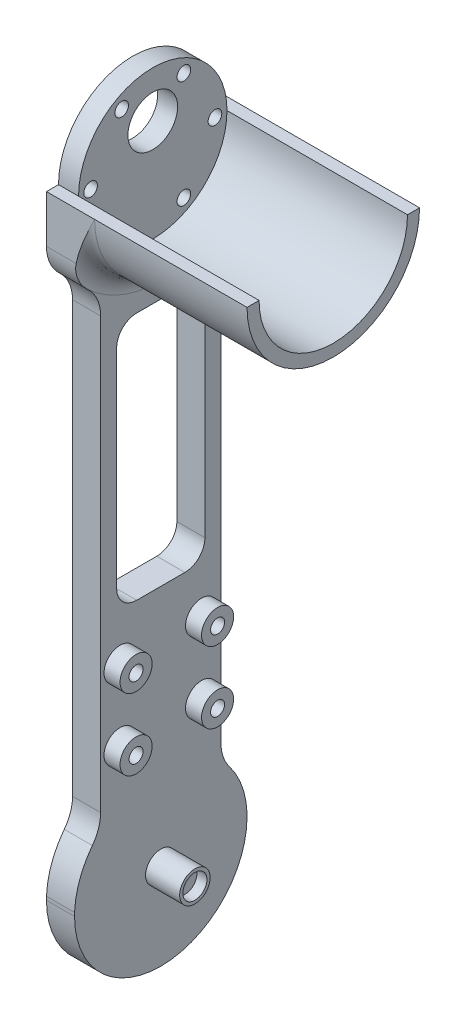
SolidWorks part; units mm, degrees
ref_plane "Front Plane" through (0, 0, 0) normal (0, 0, 1) x (1, 0, 0)
ref_plane "Top Plane" through (0, 0, 0) normal (0, 1, 0) x (1, 0, 0)
ref_plane "Right Plane" through (0, 0, 0) normal (1, 0, 0) x (0, 0, -1)
sketch "Sketch1" plane through (0, 0, 0) normal (1, 0, 0) x (0, 0, -1)
  circle A0 centre (0, 0) radius 18.5
  dimension "D1" = 37
extrude "Boss-Extrude1" add sketch "Sketch1" along normal blind 5
sketch "Sketch2" plane through (5, 0, 0) normal (1, 0, 0) x (0, 0, -1)
  circle A0 centre (0, 7) radius 6.2
  dimension "D1" = 12.4
  dimension "D2" = 7
extrude "Cut-Extrude1" cut sketch "Sketch2" against normal blind 10
sketch "Sketch3" plane through (0, 0, 0) normal (1, 0, 0) x (0, 0, -1)
  line L0 (0, 0) -> (0, 15.5) construction
  line L1 (0, 0) -> (7.75, 13.4234) construction
  line L2 (0, 0) -> (-15.5, 0) construction
  circle A0 centre (0, 0) radius 15.5 construction
  circle A1 centre (15.5, 0) radius 1.7
  circle A2 centre (7.75, -13.4234) radius 1.7
  circle A3 centre (-7.75, -13.4234) radius 1.7
  circle A4 centre (-15.5, 0) radius 1.7
  circle A5 centre (-7.75, 13.4234) radius 1.7
  circle A6 centre (7.75, 13.4234) radius 1.7
  point P17 (0, 0)
  dimension "D1" = 31
  dimension "D2" = 3.4
  dimension "D4" = 30
  dimension "D3" = 6
extrude "Cut-Extrude2" cut sketch "Sketch3" along normal blind 10
sketch "Sketch4" plane through (0, 0, 0) normal (-1, 0, 0) x (0, 0, 1)
  line L0 (-18.5, 0) -> (-21.5, 0)
  line L1 (18.5, 0) -> (21.5, 0)
  arc A0 (-21.5, 0) -> (21.5, 0) centre (0, 0) ccw
  circle A1 centre (0, 0) radius 18.5 construction
  arc A2 (-18.5, 0) -> (18.5, 0) centre (0, 0) ccw
  dimension "D1" = 3
extrude "Boss-Extrude2" add sketch "Sketch4" against normal blind 50
sketch "Sketch5" plane through (0, 0, 0) normal (-1, 0, 0) x (0, 0, 1)
  line L0 (-21.5, 0) -> (-18.5, 0)
  line L1 (18.5, 0) -> (21.5, 0)
  line L2 (-21.5, 0) -> (-21.5, -174.5)
  line L3 (21.5, 0) -> (21.5, -174.5)
  line L4 (21.5, -174.5) -> (-21.5, -174.5)
  arc A1 (-18.5, 0) -> (18.5, 0) centre (0, 0) ccw
  dimension "D1" = 174.5
extrude "Boss-Extrude3" add sketch "Sketch5" against normal blind 7
sketch "Sketch6" plane through (7, 0, 0) normal (1, 0, 0) x (0, 0, -1)
  line L0 (21.5, -174.5) -> (-21.5, -174.5) construction
  line L1 (21.5, 0) -> (21.5, -174.5) construction
  circle A0 centre (0, -153) radius 21.5
  line M3 (-21.5, 0) -> (-21.5, -174.5)
  line M4 (-21.5, -174.5) -> (21.5, -174.5)
  line M5 (21.5, -174.5) -> (21.5, 0)
  dimension "D1" = 43
extrude "Cut-Extrude3" cut sketch "Sketch6" against normal blind 20 contours A0 M3 M4 | A0 M4 M5 region at (7, -169.6976, -16.6976) region at (7, -169.6976, 16.6976)
sketch "Sketch7" plane through (7, 0, 0) normal (1, 0, 0) x (0, 0, -1)
  circle A0 centre (0, -153) radius 3.8
  dimension "D1" = 7.6
extrude "Boss-Extrude4" add sketch "Sketch7" along normal blind 8.5 and the other way blind 15.5
sketch "Sketch8" plane through (7, 0, 0) normal (1, 0, 0) x (0, 0, -1)
  line L0 (0, 7) -> (0, -113) construction
  line L1 (-6.2, 7) -> (6.2, 7) construction
  line L2 (-10.16, -121.89) -> (10.16, -121.89) construction
  line L3 (-10.16, -121.89) -> (-10.16, -104.11) construction
  line L4 (-10.16, -104.11) -> (10.16, -104.11) construction
  line L5 (10.16, -121.89) -> (10.16, -104.11) construction
  line L6 (-10.16, -121.89) -> (10.16, -104.11) construction
  line L7 (-10.16, -104.11) -> (10.16, -121.89) construction
  circle A0 centre (-10.16, -104.11) radius 1.75
  circle A1 centre (10.16, -104.11) radius 1.75
  circle A2 centre (-10.16, -121.89) radius 1.75
  circle A3 centre (10.16, -121.89) radius 1.75
  circle A4 centre (10.16, -121.89) radius 4
  circle A5 centre (-10.16, -121.89) radius 4
  circle A6 centre (-10.16, -104.11) radius 4
  circle A7 centre (10.16, -104.11) radius 4
  circle A8 centre (0, 7) radius 6.2 construction
  dimension "D4" = 8
  dimension "D5" = 3.5
  dimension "D6" = 3.5
  dimension "D7" = 8
  dimension "D8" = 3.5
  dimension "D9" = 8
  dimension "D10" = 3.5
  dimension "D11" = 8
  dimension "D1" = 120
  dimension "D2" = 20.32
  dimension "D3" = 17.78
extrude "Boss-Extrude5" add sketch "Sketch8" along normal blind 4
extrude "Cut-Extrude4" cut sketch "Sketch8<2>" against normal blind 2 contours A2 | A0 | A1 | A3 region at (7, -104.11, 10.16) region at (7, -104.11, -10.16) region at (7, -121.89, 10.16) region at (7, -121.89, -10.16)
sketch "Sketch8<2>" plane through (7, 0, 0) normal (1, 0, 0) x (0, 0, -1) same geometry as "Sketch8"
fillet "Fillet1" radius 5 1 edges at (7, -21.5, 0)
sketch "Sketch9" plane through (15.5, 0, 0) normal (1, 0, 0) x (0, 0, -1)
  circle A0 centre (0, -153) radius 3
  dimension "D1" = 6
extrude "Cut-Extrude5" cut sketch "Sketch9" against normal blind 2.5
sketch "Sketch10" plane through (7, 0, 0) normal (1, 0, 0) x (0, 0, -1)
  line L0 (-15, -21.8461) -> (-15, -137.573)
  line L1 (15, -21.8461) -> (15, -137.573)
  line L2 (-21.5, -153) -> (-21.5, -15.4919) construction
  line L3 (21.5, -15.4919) -> (21.5, -153) construction
  line L5 (-21.5, -15.4919) -> (-21.5, -153)
  line L8 (21.5, -15.4919) -> (21.5, -153.8622)
  arc A0 (-21.5, -15.4919) -> (21.5, -15.4919) centre (0, 0) ccw construction
  arc A3 (15, -21.8461) -> (21.5, -15.4919) centre (0, 0) ccw
  arc A4 (21.5, -153.8622) -> (15, -137.573) centre (0, -153) ccw
  arc A5 (-15, -137.573) -> (-21.5, -152.1378) centre (0, -153) ccw
  arc A6 (-21.5, -15.4919) -> (-15, -21.8461) centre (0, 0) ccw
  point P7 (-15, -137.573)
  point P11 (0, 0)
  point P20 (-21.5, -153)
  point P23 (21.4827, -153.8615)
  point P25 (15, -137.573)
  point P28 (-21.5, -153)
  arc M16 (21.5, -15.4919) -> (-21.5, -15.4919) centre (0, 0) cw
  line M17 (-21.5, -15.4919) -> (-21.5, -153)
  dimension "D2" = 6.5
  dimension "D3" = 6.5
extrude "Cut-Extrude6" cut sketch "Sketch10" against normal through all contours A5 L0 M16 M17 | A4 L8 L1 M16 region at (7, -80.7205, 18.3301) region at (7, -80.7205, -18.3301)
fillet "Fillet2" radius 10 6 edges at (3.5, -137.573, 15) (3.5, -137.573, -15) (3.5, -21.8461, -15) (3.5, -15.4919, -21.5) (3.5, -21.8461, 15) (3.5, -15.4919, 21.5)
sketch "Sketch11" plane through (7, 0, 0) normal (1, 0, 0) x (0, 0, -1)
  line L0 (15, -26.5942) -> (15, -133.8078) construction
  line L1 (-11, -92.4732) -> (11, -92.4732)
  line L2 (-11, -92.4732) -> (-11, -30.4732)
  line L3 (-11, -30.4732) -> (11, -30.4732)
  line L4 (11, -92.4732) -> (11, -30.4732)
  line L5 (-11, -92.4732) -> (11, -30.4732) construction
  line L6 (-11, -30.4732) -> (11, -92.4732) construction
  line L7 (-15, -26.5942) -> (-15, -133.8078) construction
  point P0 (0, -61.4732)
  point P9 (0, -59.6722)
  point P10 (0, -61.4732)
  dimension "D1" = 4
  dimension "D2" = 4
  dimension "D3" = 62
extrude "Cut-Extrude7" cut sketch "Sketch11" against normal through all
fillet "Fillet3" radius 5 4 edges at (3.5, -30.4732, 11) (3.5, -30.4732, -11) (3.5, -92.4732, -11) (3.5, -92.4732, 11)
